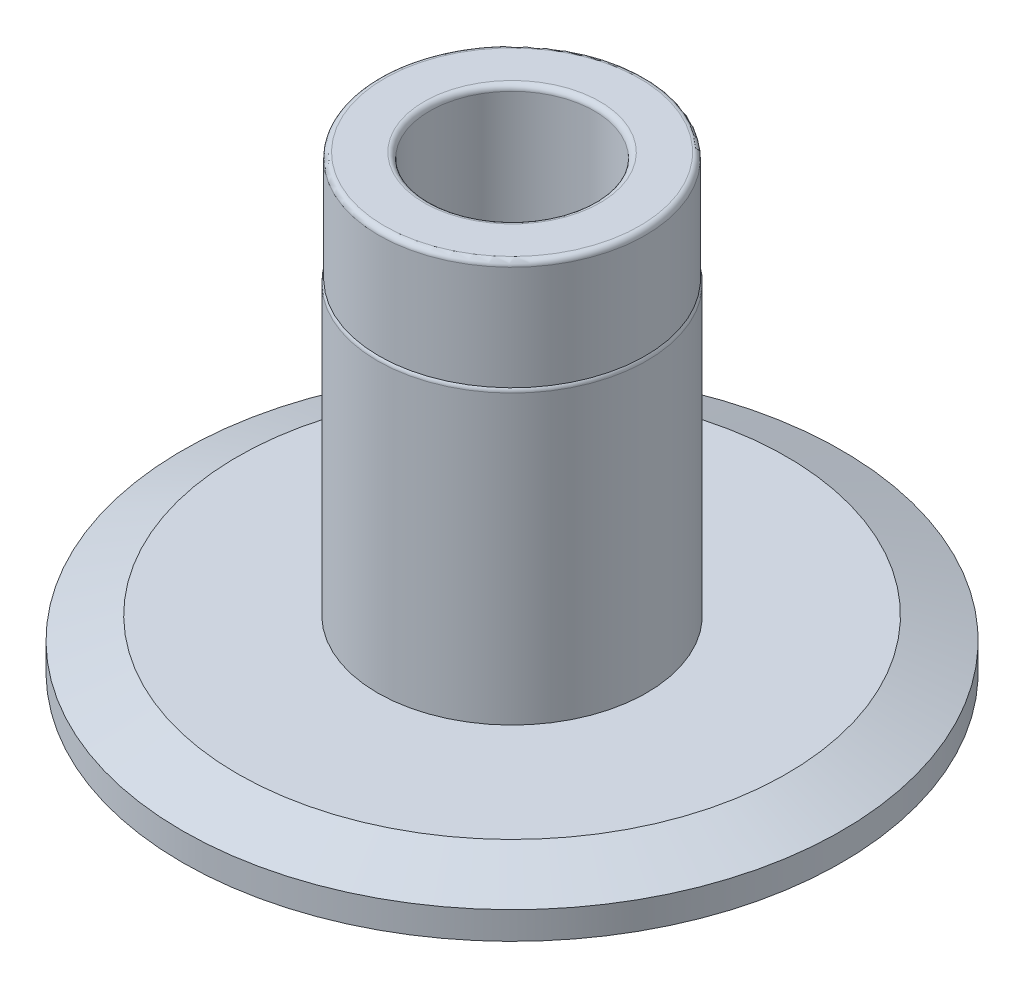
SolidWorks part; units mm, degrees
ref_plane "前视基准面" through (0, 0, 0) normal (0, 0, 1) x (1, 0, 0)
ref_plane "上视基准面" through (0, 0, 0) normal (0, 1, 0) x (1, 0, 0)
ref_plane "右视基准面" through (0, 0, 0) normal (1, 0, 0) x (0, 0, -1)
sketch "草图1" plane through (0, 0, 0) normal (0, 1, 0) x (1, 0, 0)
  line L0 (0, 24.0455) -> (0, -27.7329) construction
  line L1 (-44.7107, 0) -> (48.7055, 0) construction
  circle A0 centre (0, 0) radius 1.5
  circle A1 centre (0, 0) radius 6
  dimension "D1" = 3
  dimension "D2" = 12
extrude "凸台-拉伸1" add sketch "草图1" along normal blind 0.9
sketch "草图2" plane through (0, 0.9, 0) normal (0, 1, 0) x (1, 0, 0)
  circle A0 centre (0, 0) radius 2.45
  circle A1 centre (0, 0) radius 1.5
  dimension "D1" = 3
  dimension "D2" = 4.9
extrude "凸台-拉伸2" add sketch "草图2" along normal blind 7.3 and the other way blind 1.3
sketch "草图3" plane through (0, 8.2, 0) normal (0, 1, 0) x (1, 0, 0)
  circle A0 centre (0, 0) radius 1.5
  circle A1 centre (0, 0) radius 2.425
  dimension "D1" = 3
  dimension "D2" = 4.85
extrude "切除-拉伸1" cut sketch "草图3" against normal blind 2 flip side to cut
fillet "圆角1" radius 0.1 4 edges at (0, 8.2, 1.5) (0, -0.4, 1.5) (0, -0.4, 2.45) (0, 8.2, 2.425)
fillet "圆角2" radius 0.1 1 edges at (0, 6.2, 2.45)
chamfer "倒角1" distance 0.4 distance2 1 1 edges at (0, 0.9, 6) first distance on face at (0, 0.9, 6)
